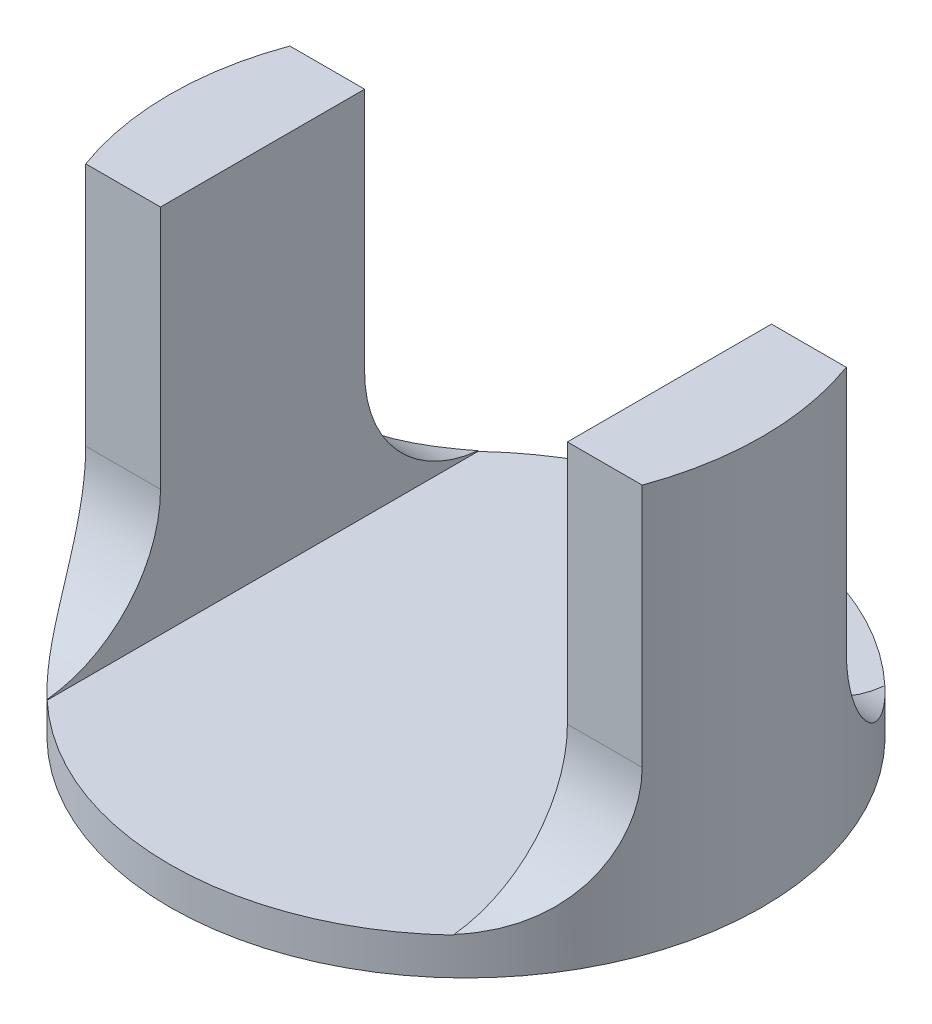
SolidWorks part; units mm, degrees
ref_plane "Front Plane" through (0, 0, 0) normal (0, 0, 1) x (1, 0, 0)
ref_plane "Top Plane" through (0, 0, 0) normal (0, 1, 0) x (1, 0, 0)
ref_plane "Right Plane" through (0, 0, 0) normal (1, 0, 0) x (0, 0, -1)
sketch "Sketch1" plane through (0, 0, 0) normal (0, 1, 0) x (1, 0, 0)
  circle A0 centre (0, 0) radius 101.6
  dimension "D1" = 203.2
extrude "Boss-Extrude1" add sketch "Sketch1" along normal blind 12.7
sketch "Sketch2" plane through (0, 12.7, 0) normal (0, 1, 0) x (1, 0, 0)
  line L0 (0, -148.3769) -> (0, 148.3769) construction
  line L1 (-191.7926, 0) -> (191.7926, 0) construction
  line L2 (69.7492, 34.9877) -> (95.3856, -34.9877) construction
  line L3 (-69.7492, -34.9877) -> (-95.3856, -34.9877)
  line L4 (-69.7492, -34.9877) -> (-69.7492, 34.9877)
  line L5 (-69.7492, 34.9877) -> (-95.3856, 34.9877)
  line L7 (-69.7492, -34.9877) -> (-95.3856, 34.9877) construction
  line L8 (-69.7492, 34.9877) -> (-95.3856, -34.9877) construction
  line L9 (69.7492, -34.9877) -> (95.3856, 34.9877) construction
  line L11 (69.7492, 34.9877) -> (95.3856, 34.9877)
  line L12 (69.7492, -34.9877) -> (95.3856, -34.9877)
  line L13 (69.7492, -34.9877) -> (69.7492, 34.9877)
  circle A0 centre (0, 0) radius 101.6 construction
  arc A1 (-95.3856, 34.9877) -> (-95.3856, -34.9877) centre (0, 0) ccw
  arc A2 (95.3856, -34.9877) -> (95.3856, 34.9877) centre (0, 0) ccw
  point P0 (-82.5674, 0)
  point P4 (0, 0)
  point P8 (0, 0)
  point P19 (82.5674, 0)
extrude "Boss-Extrude3" add sketch "Sketch2" along normal blind 127
fillet "Fillet3" radius 43.18 4 edges at (82.5674, 12.7, 34.9877) (82.5674, 12.7, -34.9877) (-82.5674, 12.7, -34.9877) (-82.5674, 12.7, 34.9877)
